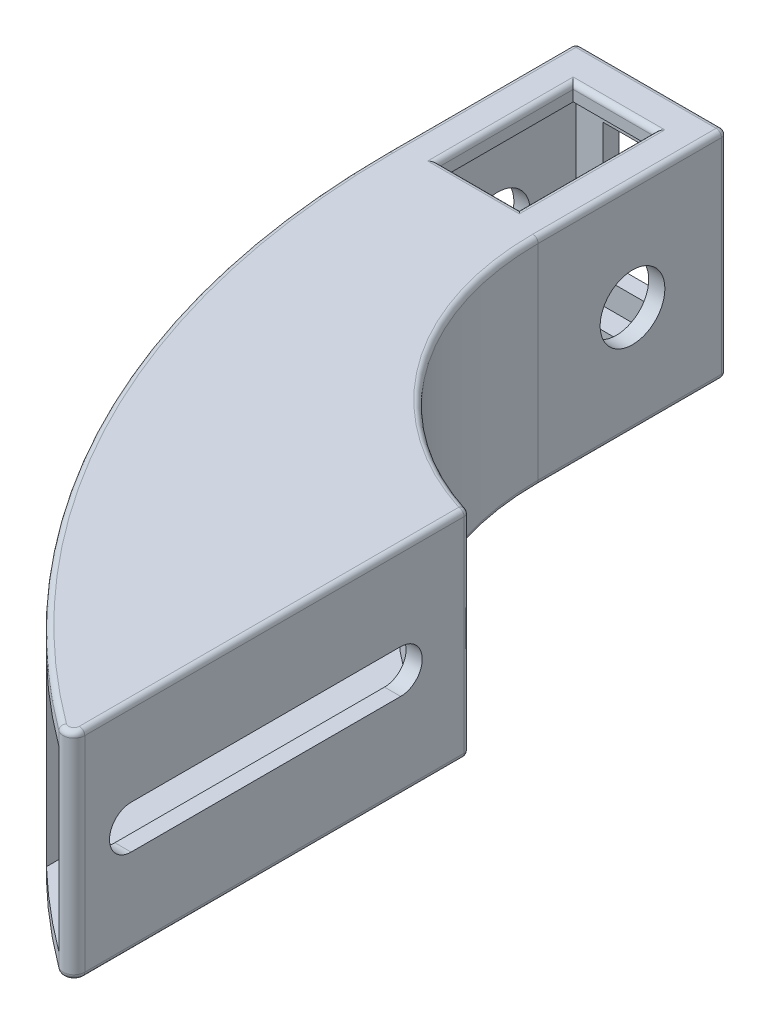
SolidWorks part; units mm, degrees
ref_plane "Front Plane" through (0, 0, 0) normal (0, 0, 1) x (1, 0, 0)
ref_plane "Top Plane" through (0, 0, 0) normal (0, 1, 0) x (1, 0, 0)
ref_plane "Right Plane" through (0, 0, 0) normal (1, 0, 0) x (0, 0, -1)
sketch "Sketch2" plane through (0, 0, 0) normal (0, 1, 0) x (1, 0, 0)
  line L0 (65, 0) -> (65, 75)
  line L1 (28, 160) -> (0, 160)
  line L2 (0, 160) -> (0, 125)
  line L3 (28, 160) -> (28, 125)
  arc A0 (28, 125) -> (65, 75) centre (80.2838, 125) ccw
  arc A1 (0, 125) -> (65, 0) centre (152.6923, 125) ccw
  dimension "D1" = 75
  dimension "D2" = 28
  dimension "D3" = 65
  dimension "D4" = 160
  dimension "D5" = 35
extrude "Boss-Extrude1" add sketch "Sketch2" along normal mid plane 40
shell "Shell1" thickness 3
sketch "Sketch3" plane through (65, 0, 0) normal (1, 0, 0) x (0, 0, -1)
  line L0 (12.5, 0) -> (62.5, 0) construction
  line L1 (12.5, 4) -> (62.5, 4)
  line L2 (12.5, -4) -> (62.5, -4)
  line L3 (37.5, 20) -> (37.5, 0) construction
  line L4 (0, 20) -> (75, 20) construction
  arc A0 (12.5, 4) -> (12.5, -4) centre (12.5, 0) ccw
  arc A1 (62.5, -4) -> (62.5, 4) centre (62.5, 0) ccw
  point P3 (37.5, 0)
  dimension "D1" = 8
  dimension "D2" = 50
extrude "Cut-Extrude1" cut sketch "Sketch3" against normal up to next
sketch "Sketch4" plane through (0, 20, 0) normal (0, 1, 0) x (1, 0, 0)
  line L0 (14, 160) -> (14, 140.5) construction
  line L1 (6.5, 153) -> (21.5, 153)
  line L2 (6.5, 153) -> (6.5, 128)
  line L3 (6.5, 128) -> (21.5, 128)
  line L4 (21.5, 153) -> (21.5, 128)
  line L5 (6.5, 153) -> (21.5, 128) construction
  line L6 (6.5, 128) -> (21.5, 153) construction
  line L7 (28, 160) -> (0, 160) construction
  point P0 (14, 140.5)
  dimension "D1" = 25
  dimension "D2" = 15
  dimension "D3" = 7
extrude "Cut-Extrude2" cut sketch "Sketch4" against normal through all
sketch "Sketch5" plane through (0, 0, -160) normal (0, 0, -1) x (-1, 0, 0)
  line L0 (-14, 20) -> (-14, -20) construction
  line L1 (-28, 20) -> (0, 20) construction
  line L2 (-28, -20) -> (0, -20) construction
  line L4 (-8, 12.5) -> (-20, 12.5)
  line L5 (-8, 12.5) -> (-8, -12.5)
  line L6 (-8, -12.5) -> (-20, -12.5)
  line L7 (-20, 12.5) -> (-20, -12.5)
  line L8 (-8, 12.5) -> (-20, -12.5) construction
  line L9 (-8, -12.5) -> (-20, 12.5) construction
  point P6 (-14, 0)
  dimension "D1" = 25
  dimension "D2" = 12
extrude "Cut-Extrude3" cut sketch "Sketch5" against normal up to next
sketch "Sketch6" plane through (28, 0, 0) normal (1, 0, 0) x (0, 0, -1)
  line L0 (160, 0) -> (125, 0) construction
  line L1 (160, 20) -> (160, -20) construction
  line L2 (125, 20) -> (125, -20) construction
  circle A0 centre (142.5, 0) radius 6
  dimension "D1" = 12
extrude "Cut-Extrude4" cut sketch "Sketch6" against normal through all
sketch "Sketch7" plane through (0, 0, 0) normal (0, 0, 1) x (1, 0, 0)
  line L0 (65, 20) -> (65, -20) construction
  line L1 (47, 16.5) -> (62, 16.5)
  line L2 (47, 16.5) -> (47, -16.5)
  line L3 (47, -16.5) -> (62, -16.5)
  line L4 (62, 16.5) -> (62, -16.5)
  line L5 (47, 16.5) -> (62, -16.5) construction
  line L6 (47, -16.5) -> (62, 16.5) construction
  point P0 (54.5, 0)
  dimension "D1" = 15
  dimension "D2" = 33
  dimension "D3" = 3
extrude "Cut-Extrude5" cut sketch "Sketch7" against normal up to next
fillet "Fillet1" radius 2 1 edges at (65, 0, 0)
fillet "Fillet2" radius 1 25 edges at (65, 0, -75) (38.2559, -20, -93.8994) (28, -20, -142.5) (14, -20, -160) (0, -20, -142.5) (16.3251, -20, -56.3056) (63.8998, -20, -2.121) (65, -20, -39.4536) (6.5, -20, -140.5) (14, -20, -153) (21.5, -20, -140.5) (14, -20, -128) (0, 20, -142.5) (14, 20, -160) (28, 20, -142.5) (38.2559, 20, -93.8994) (65, 20, -39.4536) (63.8998, 20, -2.121) (16.3251, 20, -56.3056) (14, 20, -153) (6.5, 20, -140.5) (14, 20, -128) (21.5, 20, -140.5) (0, 0, -160) (28, 0, -160)
